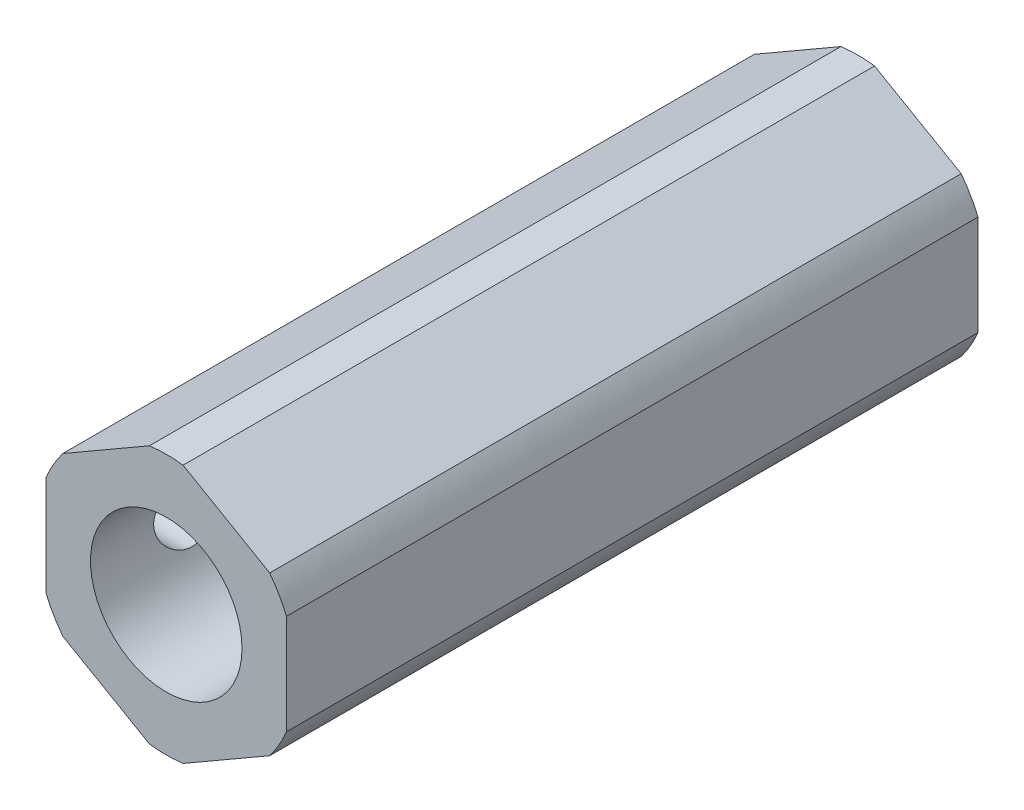
SolidWorks part; units mm, degrees
material "ThunderHex"
ref_plane "Front Plane" through (0, 0, 0) normal (0, 0, 1) x (1, 0, 0)
ref_plane "Top Plane" through (0, 0, 0) normal (0, 1, 0) x (1, 0, 0)
ref_plane "Right Plane" through (0, 0, 0) normal (1, 0, 0) x (0, 0, -1)
ref_plane "End1" through (0, 0, 18.2562) normal (0, 0, 1) x (1, 0, 0)
ref_plane "End2" through (0, 0, -18.2562) normal (0, 0, 1) x (1, 0, 0)
sketch "Sketch1" plane through (0, 0, 0) normal (0, 0, 1) x (1, 0, 0)
  circle A0 centre (0, 0) radius 6.35
  dimension "D1" = 12.7
extrude "Basic Rod" add sketch "Sketch1" along normal up to surface (18.2563 mm away) and the other way up to surface (18.2563 mm away) up to plane "End1" other way up to plane "End2"
ref_axis "Center Axis" through (0, 0, -19.2087) along (0, 0, 1)
sketch "Sketch8" plane through (0, 0, 0) normal (0, 0, 1) x (1, 0, 0)
  line L0 (-5.4616, 4.1791) -> (-6.35, 3.6662) construction
  line L1 (-0.8884, 6.8194) -> (-5.4616, 4.1791)
  line L2 (-6.35, 2.6403) -> (-6.35, -2.6403)
  line L3 (-5.4616, -4.1791) -> (-0.8884, -6.8194)
  line L4 (0.8884, -6.8194) -> (5.4616, -4.1791)
  line L5 (6.35, -2.6403) -> (6.35, 2.6403)
  line L6 (5.4616, 4.1791) -> (0.8884, 6.8194)
  line L7 (-6.35, 3.6662) -> (-6.35, 2.6403) construction
  line L8 (0, 7.3323) -> (-0.8884, 6.8194) construction
  line L9 (0.8884, 6.8194) -> (0, 7.3323) construction
  line L10 (6.35, 3.6662) -> (5.4616, 4.1791) construction
  line L11 (6.35, 2.6403) -> (6.35, 3.6662) construction
  line L12 (6.35, -3.6662) -> (6.35, -2.6403) construction
  line L13 (5.4616, -4.1791) -> (6.35, -3.6662) construction
  line L14 (0, -7.3323) -> (0.8884, -6.8194) construction
  line L15 (-0.8884, -6.8194) -> (0, -7.3323) construction
  line L16 (-6.35, -3.6662) -> (-5.4616, -4.1791) construction
  line L17 (-6.35, -2.6403) -> (-6.35, -3.6662) construction
  circle A0 centre (0, 0) radius 6.35 construction
  arc A1 (-6.35, -2.6403) -> (-5.4616, -4.1791) centre (0, 0) ccw
  circle A2 centre (0, 0) radius 6.35 construction
  arc A3 (-6.35, 2.6403) -> (-6.35, -2.6403) centre (0, 0) ccw construction
  arc A4 (-0.8884, 6.8194) -> (-5.4616, 4.1791) centre (0, 0) ccw construction
  arc A5 (-5.4616, 4.1791) -> (-6.35, 2.6403) centre (0, 0) ccw
  arc A6 (5.4616, 4.1791) -> (0.8884, 6.8194) centre (0, 0) ccw construction
  arc A7 (0.8884, 6.8194) -> (-0.8884, 6.8194) centre (0, 0) ccw
  arc A8 (6.35, -2.6403) -> (6.35, 2.6403) centre (0, 0) ccw construction
  arc A9 (6.35, 2.6403) -> (5.4616, 4.1791) centre (0, 0) ccw
  arc A10 (0.8884, -6.8194) -> (5.4616, -4.1791) centre (0, 0) ccw construction
  arc A11 (5.4616, -4.1791) -> (6.35, -2.6403) centre (0, 0) ccw
  arc A12 (-5.4616, -4.1791) -> (-0.8884, -6.8194) centre (0, 0) ccw construction
  arc A13 (-0.8884, -6.8194) -> (0.8884, -6.8194) centre (0, 0) ccw
  dimension "D1" = 13.7541
extrude "THex" add sketch "Sketch8" along normal mid plane 36.5125
sketch "Sketch5" plane through (0, 0, 0) normal (0, 0, 1) x (1, 0, 0)
  line L1 (-3.6662, 6.35) -> (-7.3323, 0)
  line L2 (-7.3323, 0) -> (-3.6662, -6.35)
  line L3 (-3.6662, -6.35) -> (3.6662, -6.35)
  line L4 (3.6662, -6.35) -> (7.3323, 0)
  line L5 (7.3323, 0) -> (3.6662, 6.35)
  line L6 (3.6662, 6.35) -> (-3.6662, 6.35)
  circle A0 centre (0, 0) radius 6.35 construction
  circle A2 centre (0, 0) radius 6.35 construction
extrude "Hex" [suppressed] add sketch "Sketch5" along normal mid plane 36.5125
sketch "Sketch7" plane through (0, 0, 0) normal (1, 0, 0) x (0, 0, -1)
  line L0 (0, 0) -> (-50000, 0) construction
  line L1 (-18.2562, 5.9436) -> (-19.2722, 5.9436)
  line L2 (-19.2722, 5.9436) -> (-19.2722, 6.35)
  line L3 (-19.2722, 6.35) -> (-20.2883, 6.35)
  line L4 (-20.7963, 5.842) -> (-20.7963, 0)
  line L5 (-20.7963, 0) -> (-18.2563, 0)
  line L6 (-18.2563, 0) -> (-18.2562, 5.9436)
  line L7 (-20.2883, 6.35) -> (-20.7963, 5.842)
  line L8 (19.2087, 0) -> (-19.2087, 0) construction
  line L9 (-18.2562, 5.2388) -> (-18.2562, -5.2388) construction
  point P7 (-20.7963, 6.35)
  dimension "D1" = 12.7
  dimension "D4" = 1.016
  dimension "D2" = 0.4064
  dimension "D3" = 2.54
revolve "1stSnapRing" [suppressed] add sketch "Sketch7" angle 360 about axis through (0, 0, -19.2087) along (0, 0, 1)
mirror "2ndSnapRing" [suppressed] about plane through (0, 0, 0) normal (0, 0, 1)
sketch "Sketch2" plane through (0, 0, 0) normal (0, 0, 1) x (1, 0, 0)
  circle A0 centre (0, 0) radius 2.1158
  dimension "D1" = 4.2316
extrude "Internal Cut" cut sketch "Sketch2" against normal through all both and the other way through all
sketch "Sketch9" plane through (0, 0, 18.2562) normal (0, 0, 1) x (1, 0, 0)
  circle A0 centre (0, 0) radius 4
  dimension "D1" = 8
extrude "Cut-Extrude1" cut sketch "Sketch9" against normal blind 20
sketch "Sketch10" plane through (-6.35, 0, 0) normal (-1, 0, 0) x (0, 0, 1)
  line L0 (18.2562, 0) -> (13.255, 0) construction
  line L1 (18.2562, 2.6403) -> (18.2562, -2.6403) construction
  line L2 (13.255, 0) -> (5.254, 0) construction
  circle A0 centre (5.254, 0) radius 1.6662
  circle A1 centre (13.255, 0) radius 1.6662
  dimension "D1" = 3.3325
  dimension "D2" = 5.0013
  dimension "D3" = 8.001
extrude "Cut-Extrude2" cut sketch "Sketch10" against normal up to next
equation "\"Unit Measure\"= \"Length\"'in"
equation "\"D1@Sketch1\"=\"OD\""
equation "\"D1\"= \"Length\""
equation "\"D1@Sketch2\"=\"ID\""
equation "\"Internal Cut\"= IIF ( \"ID\" = 0 ,  suppressed  ,  unsuppressed  ) "
equation "\"D1@Hex\" = \"Length\""
equation "\"Hex\" = IIF ( \"SelectionType\" = 1 , \"suppressed\" , iif ( \"SelectionType\" = 2 , \"suppressed\" , \"unsuppressed\" ) )"
equation "\"OutsideDiameter\"= \"OD\"'in"
equation "\"ThunderHexDia\"= iif ( \"OD\" < .36 , \"OD\" * 1.1 , iif ( \"OD\" < .40 , .4035 , iif ( \"OD\" < .52 , .5415 , \"OD\" * 1.1 ) ) )"
equation "\"D1@Sketch7\"=\"Thickness\""
equation "\"SRDia\"= iif ( \"OD\" = .5 , ( \"OD\" - .468 ) / 2 , iif ( \"OD\" = .375 , ( \"OD\" - .352 ) / 2 , .050 ) )"
equation "\"D2@Sketch7\"= \"SnapRingDepth\""
equation "\"1stSnapRing\"= iif ( \"SnapRingCount\" > 0 , \"unsuppressed\" , \"suppressed\" )"
equation "\"2ndSnapRing\"= iif ( \"SnapRingCount\" = 2 , \"unsuppressed\" , \"suppressed\" )"
equation "\"D1@End1\" = \"Length\" / 2"
equation "\"D1@End2\" = \"Length\""
equation "\"D1@Sketch8\"=\"ThunderHexDia\""
equation "\"D1@THex\" = \"Length\""
equation "\"THex\"= IIF ( \"SelectionType\" = 0 ,  suppressed  , iif ( \"SelectionType\" = 2 ,  suppressed  ,  unsuppressed  )  ) "
